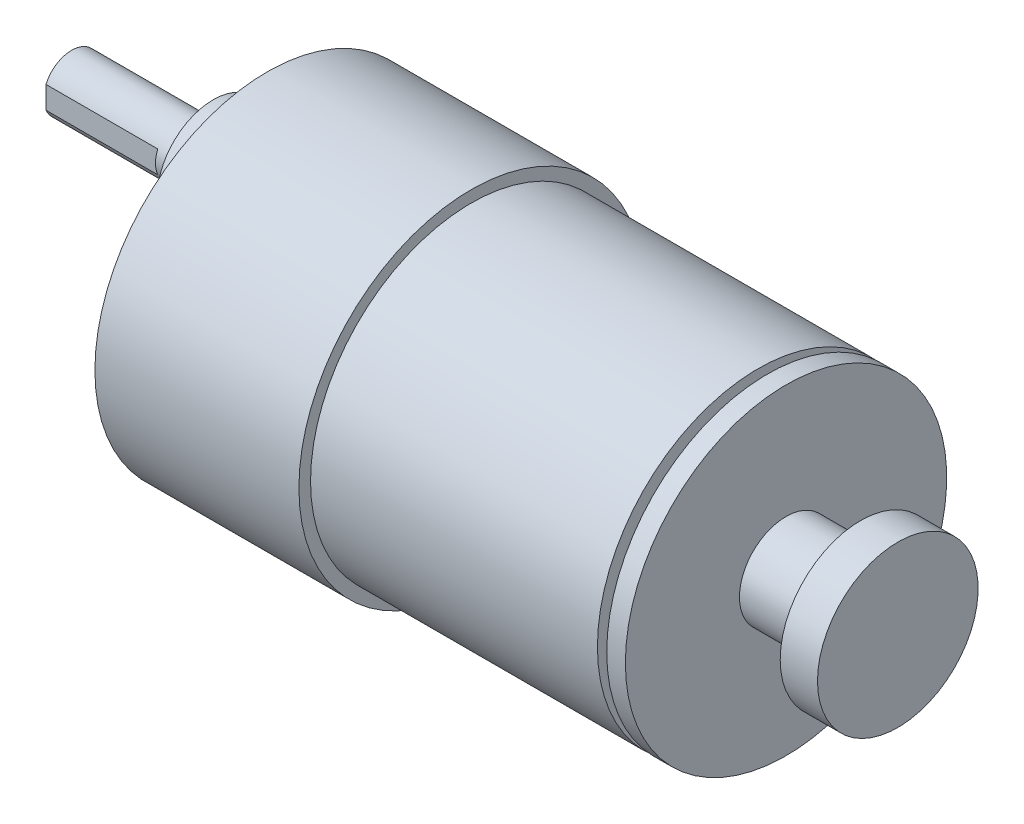
SolidWorks part; units mm, degrees
ref_plane "Front Plane" through (0, 0, 0) normal (0, 0, 1) x (1, 0, 0)
ref_plane "Top Plane" through (0, 0, 0) normal (0, 1, 0) x (1, 0, 0)
ref_plane "Right Plane" through (0, 0, 0) normal (1, 0, 0) x (0, 0, -1)
sketch "Sketch1" plane through (0, 0, 0) normal (0, 0, 1) x (1, 0, 0)
  line L0 (-80.1114, 0) -> (59.0183, 0) construction
  line L1 (0, 0) -> (0, 8.625)
  line L2 (0, 8.625) -> (-4, 8.625)
  line L3 (-4, 8.625) -> (-4, 5)
  line L4 (-4, 5) -> (-12, 5)
  line L5 (-12, 5) -> (-12, 17.25)
  line L6 (-12, 17.25) -> (-14, 17.25)
  line L7 (-14, 17.25) -> (-14, 5)
  line L8 (-14, 5) -> (-15, 5)
  line L9 (-15, 5) -> (-15, 17.25)
  line L10 (-15, 17.25) -> (-45.8, 17.25)
  line L11 (-45.8, 17.25) -> (-45.8, 18.5)
  line L12 (-45.8, 18.5) -> (-67.7, 18.5)
  line L13 (-67.7, 18.5) -> (-67.7, 0)
  line L14 (-67.7, 0) -> (0, 0)
  dimension "D1" = 34.5
  dimension "D2" = 30.8
  dimension "D3" = 37
  dimension "D4" = 21.9
  dimension "D5" = 15
  dimension "D6" = 17.25
  dimension "D7" = 1
  dimension "D8" = 2
  dimension "D9" = 10
  dimension "D10" = 4
revolve "MainBody" add sketch "Sketch1" angle 360 about L0
sketch "Sketch3" plane through (0, 0, 0) normal (0, 0, 1) x (1, 0, 0)
  line L0 (0, 0) -> (-101.2302, 0) construction
  line L1 (0, 7) -> (-101.2302, 7) construction
  line L2 (-67.7, 7) -> (-67.7, 13)
  line L4 (-67.7, 18.5) -> (-67.7, -18.5) construction
  line L5 (-67.7, 13) -> (-73.5, 13)
  line L6 (-73.5, 13) -> (-73.5, 10)
  line L7 (-73.5, 10) -> (-88.7, 10)
  line L8 (-88.7, 10) -> (-88.7, 7)
  line L9 (-88.7, 7) -> (-67.7, 7)
  dimension "D2" = 12
  dimension "D3" = 6
  dimension "D4" = 5.8
  dimension "D5" = 21
  dimension "D1" = 7
revolve "SmallBoss" add sketch "Sketch3" angle 360 about L1
sketch "Sketch4" plane through (-88.7, 0, 0) normal (-1, 0, 0) x (0, 0, 1)
  line L1 (-2.75, 10.7731) -> (2.75, 10.7731)
  line L2 (-2.75, 10.7731) -> (-2.75, 3.2269)
  line L3 (-2.75, 3.2269) -> (2.75, 3.2269)
  line L4 (2.75, 10.7731) -> (2.75, 3.2269)
  line L5 (-2.75, 10.7731) -> (2.75, 3.2269) construction
  line L6 (-2.75, 3.2269) -> (2.75, 10.7731) construction
  circle A0 centre (0, 7) radius 3 construction
  circle A1 centre (0, 7) radius 3
  point P0 (0, 7)
  point P1 (0, 7)
  circle M5 centre (0, 7) radius 3
  dimension "D1" = 5.5
extrude "Cut-Extrude1" cut sketch "Sketch4" against normal blind 12 contours L2 M5 | L4 M5 region at (-88.7, 7, -2.8504) region at (-88.7, 7, 2.8504)
hole_wizard "M3x0.5 Tapped Hole1" positions "Sketch7" profile "Sketch8" tap size "M3x0.5" standard "ANSI Metric"
sketch "Sketch7" plane through (-67.7, 0, 0) normal (-1, 0, 0) x (0, 0, 1)
  circle A0 centre (0, 0) radius 15.5 construction
  point P5 (15.5, 0)
  point P11 (7.75, -13.4234)
  point P12 (-7.75, -13.4234)
  point P13 (-15.5, 0)
  point P14 (-7.75, 13.4234)
  point P15 (7.75, 13.4234)
  dimension "D1" = 31
  dimension "D2" = 6
sketch "Sketch8" plane through (-67.7, 13.4234, 7.75) normal (0, 1, 0) x (0, 0, 1)
  line L0 (0, 0) -> (0, 9.2511)
  line L1 (0, 9.2511) -> (1.25, 8.5)
  line L2 (1.25, 8.5) -> (1.25, 0)
  line L5 (1.25, 0) -> (0, 0)
  line L10 (0, 9.2511) -> (-1.25, 8.5) construction
  line L11 (0, -6.35) -> (0, 107.95) construction
  dimension "Tap Drill Dia." = 2.5
  dimension "Tap Drill Depth" = 8.5
  dimension "Drill Angle" = 118
cosmetic thread "Hole Thread1" parameters "D1"=6, "D2"=3
cosmetic thread "Hole Thread2" parameters "D1"=6, "D2"=3
cosmetic thread "Hole Thread3" parameters "D1"=6, "D2"=3
cosmetic thread "Hole Thread4" parameters "D1"=6, "D2"=3
cosmetic thread "Hole Thread5" parameters "D1"=6, "D2"=3
cosmetic thread "Hole Thread6" parameters "D1"=6, "D2"=3
sketch "Sketch9" plane through (-67.7, 0, 0) normal (-1, 0, 0) x (0, 0, 1)
  circle A0 centre (0, 0) radius 11.3016
  circle A1 centre (0, 7) radius 9.3451
extrude "Cut-Extrude2" cut sketch "Sketch9" against normal blind 2 contours A1 A0 region at (-67.7, -4.1669, 0)
